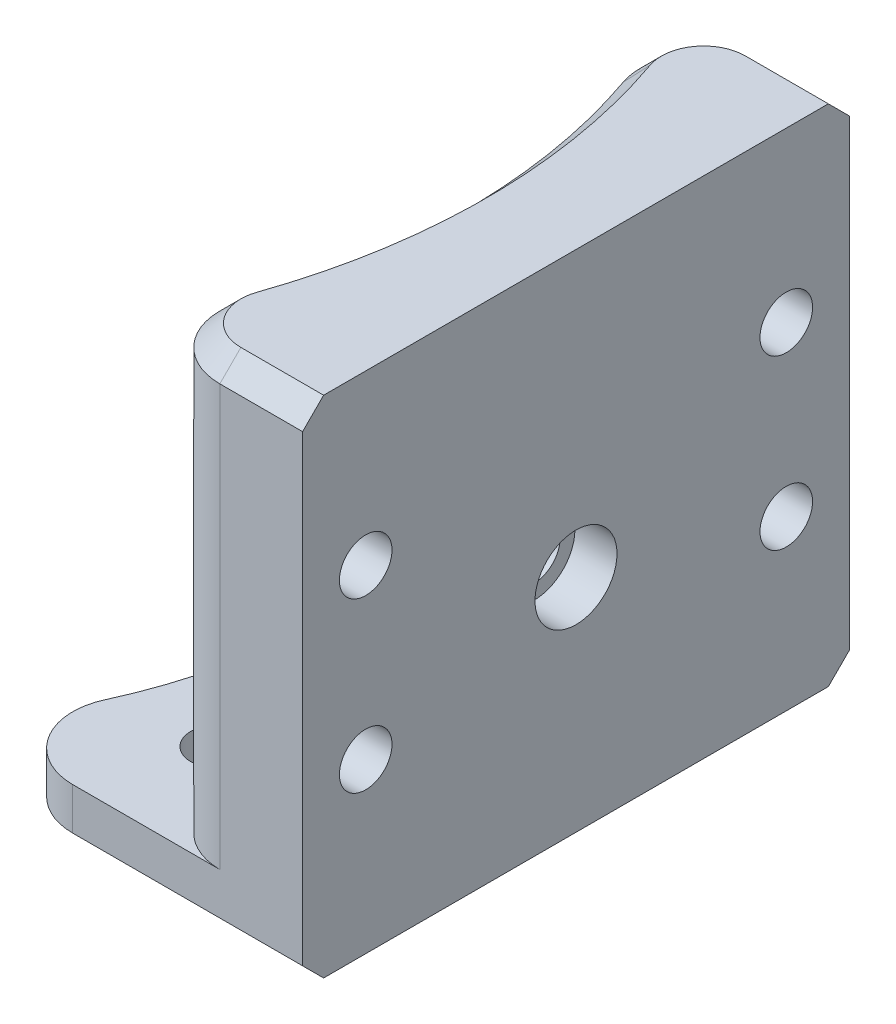
SolidWorks part; units mm, degrees
ref_plane "Спереди" through (0, 0, 0) normal (0, 0, 1) x (1, 0, 0)
ref_plane "Сверху" through (0, 0, 0) normal (0, 1, 0) x (1, 0, 0)
ref_plane "Справа" through (0, 0, 0) normal (1, 0, 0) x (0, 0, -1)
sketch "Эскиз1" plane through (0, 0, 0) normal (0, 1, 0) x (1, 0, 0)
  line L0 (23.6854, 8) -> (23.6854, -8) construction
  line L1 (16.4924, 13) -> (32.75, 13)
  line L2 (16.4924, 13) -> (16.4924, -13) construction
  line L3 (16.4924, -13) -> (32.75, -13)
  line L4 (32.75, 13) -> (32.75, -13)
  circle A0 centre (0, 0) radius 25 construction
  circle A2 centre (0, 0) radius 21
  circle A3 centre (23.6854, 8) radius 1.25
  circle A4 centre (23.6854, -8) radius 1.25
  dimension "D1" = 50
  dimension "D6" = 2.5
  dimension "D7" = 2.5
  dimension "D3" = 26
  dimension "D4" = 32.75
  dimension "D5" = 16
extrude "Бобышка-Вытянуть1" add sketch "Эскиз1" along normal blind 24 contours A2 L3 L4 L1 A4 A3 region at (26.1643, 0, 0)
sketch "Эскиз2" plane through (0, 24, 0) normal (0, 1, 0) x (1, 0, 0)
  circle A0 centre (0, 0) radius 25 construction
  circle A1 centre (0, 0) radius 27.5
  dimension "D1" = 2.5
extrude "Вырез-Вытянуть1" cut sketch "Эскиз2" against normal offset from surface (21 mm away) 3 up to face at (23.6854, 0, 9.25)
fillet "Скругление1" radius 3 4 edges at (24.2332, 13.5, 13) (24.2332, 13.5, -13) (16.4924, 1.5, -13) (16.4924, 1.5, 13)
sketch "Эскиз3" plane through (32.75, 0, 0) normal (1, 0, 0) x (0, 0, -1)
  line L0 (13, 0) -> (-13, 0) construction
  line L1 (-13, 12) -> (13, 12) construction
  line L2 (-10, 16) -> (-10, 8) construction
  line L3 (0, 0) -> (0, 24) construction
  line L4 (13, 24) -> (-13, 24) construction
  line L5 (-13, 24) -> (-13, 0) construction
  line L6 (13, 24) -> (13, 0) construction
  circle A0 centre (0, 10.5) radius 1.25
  circle A2 centre (-10, 16) radius 1.25
  circle A3 centre (-10, 8) radius 1.25
  circle A4 centre (10, 8) radius 1.25
  circle A5 centre (10, 16) radius 1.25
  point P4 (0, 0)
  point P17 (-13, 12)
  dimension "D1" = 2.5
  dimension "D3" = 2.5
  dimension "D2" = 10.5
  dimension "D4" = 8
  dimension "D5" = 20
extrude "Вырез-Вытянуть2" cut sketch "Эскиз3" against normal through all
chamfer "Фаска2" distance 1 angle 45 10 edges at (30.782, 24, -13) (26.3696, 24, -11.7391) (27.5, 24, 0) (30.782, 24, 13) (26.3696, 24, 11.7391) (27.2837, 0, -13) (19.2925, 0, -11.6202) (21, 0, 0) (19.2925, 0, 11.6202) (27.2837, 0, 13)
sketch "Эскиз4" plane through (0, 0, 0) normal (1, 0, 0) x (0, 0, -1)
  line L0 (-13, 12) -> (13, 12) construction
  line L1 (-7.85, 14.7587) -> (-7.85, 17.2413)
  line L2 (-7.85, 17.2413) -> (-10, 18.4826)
  line L3 (-10, 18.4826) -> (-12.15, 17.2413)
  line L4 (-12.15, 17.2413) -> (-12.15, 14.7587)
  line L5 (-12.15, 14.7587) -> (-10, 13.5174)
  line L6 (-10, 13.5174) -> (-7.85, 14.7587)
  line L7 (-13, 23) -> (-13, 1) construction
  line L8 (13, 23) -> (13, 1) construction
  line L9 (0, 24) -> (0, 0) construction
  line L10 (12, 24) -> (-12, 24) construction
  line L11 (12, 0) -> (-12, 0) construction
  line L12 (-10, 10.4826) -> (-7.85, 9.2413)
  line L13 (-12.15, 9.2413) -> (-10, 10.4826)
  line L14 (-12.15, 6.7587) -> (-12.15, 9.2413)
  line L15 (-10, 5.5174) -> (-12.15, 6.7587)
  line L16 (-7.85, 6.7587) -> (-10, 5.5174)
  line L17 (-7.85, 9.2413) -> (-7.85, 6.7587)
  line L18 (7.85, 9.2413) -> (7.85, 6.7587)
  line L19 (7.85, 6.7587) -> (10, 5.5174)
  line L20 (10, 5.5174) -> (12.15, 6.7587)
  line L21 (12.15, 6.7587) -> (12.15, 9.2413)
  line L22 (12.15, 9.2413) -> (10, 10.4826)
  line L23 (10, 10.4826) -> (7.85, 9.2413)
  line L24 (10, 13.5174) -> (7.85, 14.7587)
  line L25 (12.15, 14.7587) -> (10, 13.5174)
  line L26 (12.15, 17.2413) -> (12.15, 14.7587)
  line L27 (10, 18.4826) -> (12.15, 17.2413)
  line L28 (7.85, 17.2413) -> (10, 18.4826)
  line L29 (7.85, 14.7587) -> (7.85, 17.2413)
  circle A0 centre (-10, 16) radius 2.15 construction
  dimension "D1" = 4.3
extrude "Вырез-Вытянуть3" cut sketch "Эскиз4" along normal offset from surface (28.75 mm away) 4 up to face at (32.75, 16, -8.75)
sketch "Эскиз5" plane through (32.75, 0, 0) normal (1, 0, 0) x (0, 0, -1)
  circle A0 centre (0, 10.5) radius 1.95
  dimension "D1" = 3.9
extrude "Вырез-Вытянуть4" cut sketch "Эскиз5" against normal blind 2
sketch "Эскиз6" plane through (0, 0, 0) normal (0, -1, 0) x (1, 0, 0)
  circle A0 centre (23.6854, 8) radius 1.95
  circle A1 centre (23.6854, -8) radius 1.95
  dimension "D1" = 3.9
  dimension "D2" = 3.9
extrude "Вырез-Вытянуть5" cut sketch "Эскиз6" against normal blind 1
equation "\"motor_diameter\"= 30"
equation "\"mm_diameter\"= IIF ( \"motor_diameter\" < 34 , 41 , \"motor_diameter\" + 8 )"
equation "\"upper_shafts_diameter\"= 5"
equation "\"upper_shats_length\"= 180"
equation "\"upper_bearing_d1\"= 10"
equation "\"upper_bearing_d2\"= 5"
equation "\"upper_bearing_h\"= 15"
equation "\"lower_shafts_diameter\"= 5"
equation "\"lower_shafts_length\"= 180"
equation "\"lower_bearing_d1\"= 10"
equation "\"lower_bearing_d2\"= 5"
equation "\"lower_bearing_h\"= 15"
equation "\"print_offset\"= 0.5"
equation "\"bh_screws_d\"= 2"
equation "\"bh_screws_h\"= 20"
equation "\"bh_screws_hh_d\"= 3.4"
equation "\"bh_screws_hh_h\"= 2"
equation "\"bh_nut_d\"= 3.8"
equation "\"bh_nut_h\"= 2"
equation "\"motor_screws_d\"= 3"
equation "\"motor_screws_h\"= 16"
equation "\"motor_screws_hh_d\"= 5.5"
equation "\"motor_screws_hh_h\"= 3"
equation "\"plate_hole_distance\"= 25.4"
equation "\"plate_screws_d\"= 6.5"
equation "\"shafts_diameter\"= IIF ( \"mm_diameter\" < 42 , 42 + 8 , \"mm_diameter\" + 8 )"
equation "\"central_hole_diameter\"= 8"
equation "\"bh_thikness\"= 4"
equation "\"ends_screws_d\"= 4"
equation "\"ends_screws_h\"= 16"
equation "\"ends_screws_hh_d\"= 6.7"
equation "\"ends_screws_hh_h\"= 4.1"
equation "\"ends_nut_d\"= 6.8"
equation "\"ends_nut_h\"= 3"
equation "\"system_radius\" = ( \"shafts_diameter\" + 12 + \"bh_thikness\" / 2 ) / 2"
equation "\"encoder_distance\"= \"system_radius\" + 4"
equation "\"tape_position\"= \"encoder_distance\" - 2 + 3.9 + 1.7 / 2"
equation "\"D1@Эскиз1\"=\"shafts_diameter\""
equation "\"D2@Эскиз1\"=\"bh_thikness\""
equation "\"D4@Эскиз1\"=\"tape_position\"-6"
equation "\"D6@Эскиз1\"=\"bh_screws_d\"+\"print_offset\""
equation "\"D7@Эскиз1\"=\"D6@Эскиз1\""
equation "\"D1@Бобышка-Вытянуть1\"=\"upper_bearing_h\"+6+3"
equation "\"D1@Эскиз2\"=\"bh_thikness\"/2+\"print_offset\""
equation "\"D1@Эскиз3\"=\"bh_screws_d\"+\"print_offset\""
equation "\"D2@Эскиз3\"=\"upper_bearing_h\"/2+3"
equation "\"D3@Эскиз3\"=\"bh_screws_d\"+\"print_offset\""
equation "\"D1@Эскиз4\"=\"bh_nut_d\"+\"print_offset\""
equation "\"D1@Вырез-Вытянуть3\"=12-8"
equation "\"D1@Эскиз5\"=\"bh_screws_hh_d\"+\"print_offset\""
equation "\"D1@Вырез-Вытянуть4\"=\"bh_screws_hh_h\""
equation "\"D1@Эскиз6\"=\"bh_screws_hh_d\"+\"print_offset\""
equation "\"D2@Эскиз6\"=\"D1@Эскиз6\""
